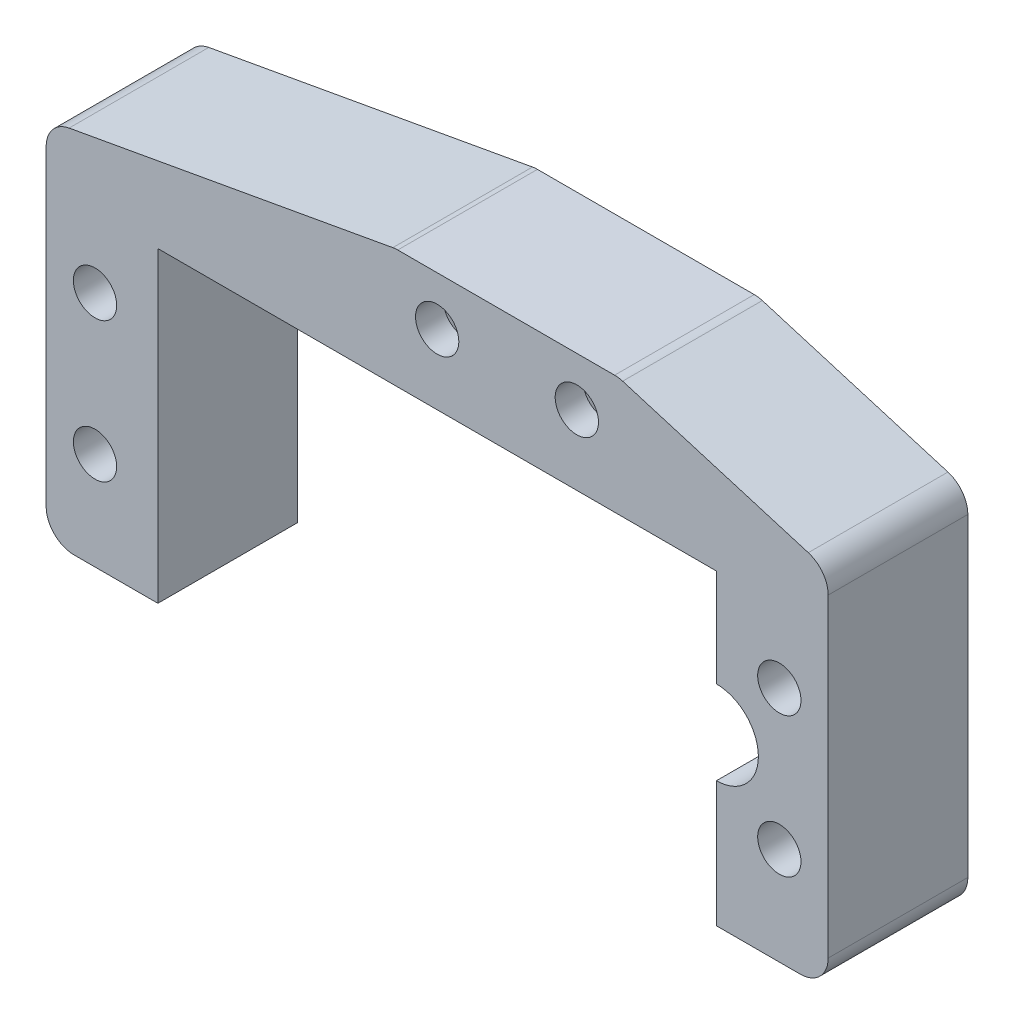
SolidWorks part; units mm, degrees
ref_plane "前视基准面" through (0, 0, 0) normal (0, 0, 1) x (1, 0, 0)
ref_plane "上视基准面" through (0, 0, 0) normal (0, 1, 0) x (1, 0, 0)
ref_plane "右视基准面" through (0, 0, 0) normal (1, 0, 0) x (0, 0, -1)
sketch "草图1" plane through (0, 0, 0) normal (0, 0, 1) x (1, 0, 0)
  line L0 (-10, 0) -> (20, 0)
  line L1 (-28, -12) -> (28, -12)
  line L2 (-28, -12) -> (-28, 12)
  line L3 (-28, 12) -> (28, 12)
  line L4 (28, -12) -> (28, 12)
  line L5 (-28, -12) -> (28, 12) construction
  line L6 (-28, 12) -> (28, -12) construction
  line L7 (-20, -10) -> (20, -10)
  line L8 (-20, -10) -> (-20, 10)
  line L9 (-20, 10) -> (20, 10)
  line L10 (20, -10) -> (20, 10)
  line L11 (-20, -10) -> (20, 10) construction
  line L12 (-20, 10) -> (20, -10) construction
  line L13 (-24.5, -5) -> (24.5, -5)
  line L14 (-24.5, -5) -> (-24.5, 5)
  line L15 (-24.5, 5) -> (24.5, 5)
  line L16 (24.5, -5) -> (24.5, 5)
  line L17 (-24.5, -5) -> (24.5, 5) construction
  line L18 (-24.5, 5) -> (24.5, -5) construction
  line L19 (0, 15) -> (10, 15)
  line L20 (-3, 12) -> (13, 12)
  line L21 (-3, 12) -> (-3, 18.5)
  line L22 (-3, 18.5) -> (13, 18.5)
  line L23 (13, 12) -> (13, 18.5)
  line L24 (-3, 18.5) -> (-10, 12)
  line L25 (-10, 12) -> (-3, 18.5)
  line L26 (13, 18.5) -> (20, 12)
  line L27 (-28, 14) -> (-3, 18.5)
  line L28 (-20, 10) -> (20, 10)
  line L29 (-20, 10) -> (-20, -12)
  line L30 (-20, -12) -> (20, -12)
  line L31 (20, 10) -> (20, -12)
  line L32 (-28, 12) -> (28, 12)
  line L33 (-28, 12) -> (-28, 14)
  line L34 (-28, 14) -> (28, 14)
  line L35 (28, 12) -> (28, 14)
  line L36 (13, 18.5) -> (28, 14)
  line L38 (1.3568, 17.35) -> (-1.3568, 17.35)
  line L39 (-1.3568, 17.35) -> (-2.7135, 15)
  line L40 (-2.7135, 15) -> (-1.3568, 12.65)
  line L41 (-1.3568, 12.65) -> (1.3568, 12.65)
  line L42 (1.3568, 12.65) -> (2.7135, 15)
  line L43 (2.7135, 15) -> (1.3568, 17.35)
  line L44 (11.3568, 17.35) -> (8.6432, 17.35)
  line L45 (8.6432, 17.35) -> (7.2865, 15)
  line L46 (7.2865, 15) -> (8.6432, 12.65)
  line L47 (8.6432, 12.65) -> (11.3568, 12.65)
  line L48 (11.3568, 12.65) -> (12.7135, 15)
  line L49 (12.7135, 15) -> (11.3568, 17.35)
  circle A0 centre (-10, 0) radius 8
  circle A1 centre (20, 0) radius 3
  circle A2 centre (-24.5, 5) radius 1.55
  circle A3 centre (-24.5, -5) radius 1.55
  circle A4 centre (24.5, -5) radius 1.55
  circle A5 centre (24.5, 5) radius 1.55
  circle A6 centre (0, 15) radius 1.55
  circle A7 centre (10, 15) radius 1.55
  circle A8 centre (0, 15) radius 2.35 construction
  circle A9 centre (10, 15) radius 2.35 construction
  point P0 (0, 0)
  point P7 (0, 0)
  point P14 (-20, 0)
  point P15 (0, 0)
  point P32 (5, 15)
  point P33 (5, 18.5)
  point P34 (5, 0)
  dimension "D7" = 16
  dimension "D8" = 6
  dimension "D18" = 3.1
  dimension "D19" = 3.1
  dimension "D20" = 3.1
  dimension "D21" = 3.1
  dimension "D22" = 3.1
  dimension "D23" = 3.1
  dimension "D1" = 24
  dimension "D2" = 56
  dimension "D3" = 40
  dimension "D4" = 20
  dimension "D5" = 30
  dimension "D6" = 10
  dimension "D9" = 10
  dimension "D10" = 49
  dimension "D11" = 10
  dimension "D12" = 16
  dimension "D13" = 15
  dimension "D14" = 3.5
  dimension "D15" = 2
  dimension "D16" = 4.7
  dimension "D17" = 4.7
extrude "凸台-拉伸3" add sketch "草图1" along normal blind 2 contours L23 L34 L26 | L36 L26 L34 | L3 L35 L34 L26 | L34 L23 L3 L26 | L49 L48 L34 L23 L22 L21 L40 L39 L38 L43 L19 L45 L44 | A7 L34 L48 L49 L44 L45 L19 | A7 L34 L46 L47 L48 | A7 L19 L46 L34 | L48 L47 L46 L34 L42 L41 L40 L21 L3 L23 | L46 L19 L42 L34 | A6 L19 L43 L38 L39 L40 L34 | A6 L34 L40 L41 L42 | A6 L34 L42 L19 | L27 L34 L24 | L24 L34 L21 | L34 L25 L3 L21 | L34 L33 L3 L25 | A5 L16 A4 L13 L10 L31 L1 L4 L3 L2 L29 L8 A3 L14 A2 L15 L9 | A3 L13 L8 L15 A2 L14 | A5 L15 L31 A1 L10 L13 A4 L16 region at (20.1097, 4, 0) region at (20.6093, 7.5, 0) region at (-22.1043, 0, 0) region at (23.4402, 13.0395, 0) region at (-18.4514, 13.0188, 0) region at (15.9942, 12.9394, 0) region at (19.6154, 15.5, 0) region at (-5.9942, 12.9394, 0) region at (-12.9487, 15.5, 0) region at (5, 12.8432, 0) region at (14.6154, 15.5, 0) region at (5, 17.0344, 0) region at (-4.6154, 15.5, 0) region at (10, 13.28, 0) region at (11.6602, 14.0638, 0) region at (-2.3696, 14.5319, 0) region at (0, 13.28, 0) region at (8.062, 14.5187, 0) region at (1.938, 14.5187, 0) region at (5, 14.4813, 0)
extrude "凸台-拉伸5" add sketch "草图1<7>" against normal blind 8 contours L49 L48 L34 L23 L22 L21 L40 L39 L38 L43 L19 L45 L44 | L46 L19 L42 L34 | L48 L47 L46 L34 L42 L41 L40 L21 L3 L23 | L36 L26 L34 | L23 L34 L26 | L34 L23 L3 L26 | L3 L35 L34 L26 | L24 L34 L21 | L34 L25 L3 L21 | L27 L34 L24 | L34 L33 L3 L25 | A5 L16 A4 L13 L10 L31 L1 L4 L3 L2 L29 L8 A3 L14 A2 L15 L9 | A5 L15 L31 A1 L10 L13 A4 L16 | A3 L13 L8 L15 A2 L14 region at (20.1097, 4, 0) region at (20.6093, 7.5, 0) region at (-22.1043, 0, 0) region at (23.4402, 13.0395, 0) region at (-18.4514, 13.0188, 0) region at (15.9942, 12.9394, 0) region at (19.6154, 15.5, 0) region at (-5.9942, 12.9394, 0) region at (-12.9487, 15.5, 0) region at (5, 12.8432, 0) region at (14.6154, 15.5, 0) region at (5, 17.0344, 0) region at (-4.6154, 15.5, 0) region at (5, 14.4813, 0)
sketch "草图1<7>" plane through (0, 0, 0) normal (0, 0, 1) x (1, 0, 0) same geometry as "草图1"
fillet "圆角4" radius 2 6 edges at (28, -12, -3) (-28, -12, -3) (-28, 14, -3) (-3, 18.5, -3) (13, 18.5, -3) (28, 14, -3)
